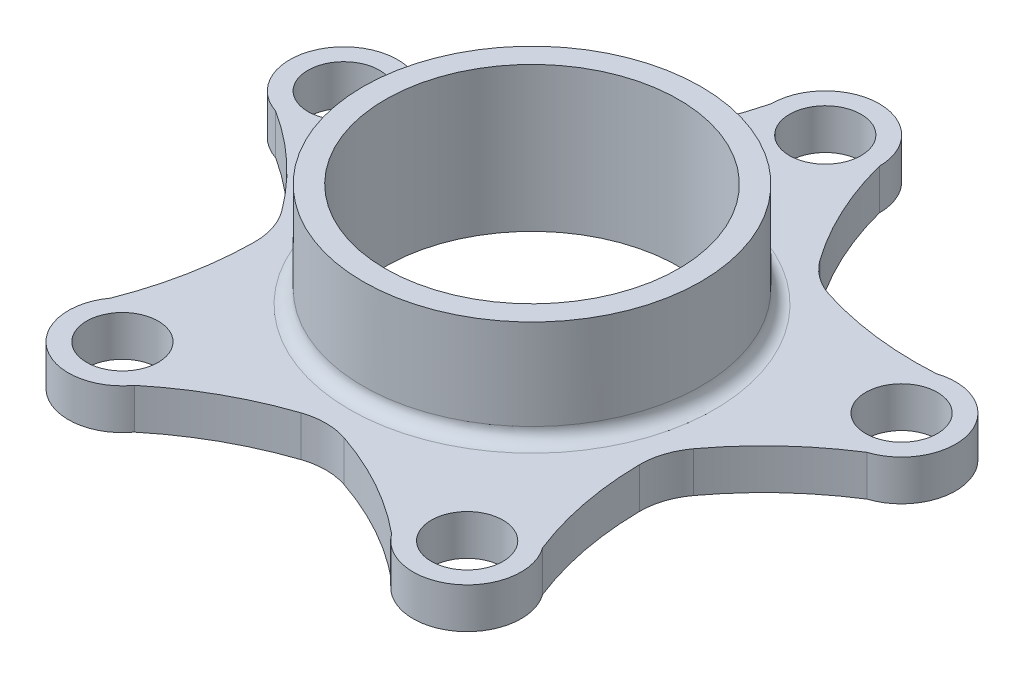
SolidWorks part; units mm, degrees
ref_plane "Front Plane" through (0, 0, 0) normal (0, 0, 1) x (1, 0, 0)
ref_plane "Top Plane" through (0, 0, 0) normal (0, 1, 0) x (1, 0, 0)
ref_plane "Right Plane" through (0, 0, 0) normal (1, 0, 0) x (0, 0, -1)
sketch "Sketch1" plane through (0, 0, 0) normal (0, 1, 0) x (1, 0, 0)
  circle A0 centre (0, 0) radius 31.75
  dimension "D1" = 63.5
extrude "CenterCircleExtrude" add sketch "Sketch1" along normal blind 19.558 contours A0
sketch "Sketch2" plane through (0, 0, 0) normal (0, -1, 0) x (1, 0, 0)
  circle A0 centre (0, 0) radius 80.01
  dimension "D1" = 160.02
extrude "BaseExpand" add sketch "Sketch2" along normal blind 7.62
sketch "Sketch3" plane through (0, 19.558, 0) normal (0, 1, 0) x (1, 0, 0)
  circle A0 centre (0, 0) radius 27.559
  dimension "D1" = 55.118
extrude "CenterCut" cut sketch "Sketch3" against normal blind 27.178 contours A0
sketch "Sketch4" plane through (0, 0, 0) normal (0, 1, 0) x (1, 0, 0)
  line L0 (-52.4203, 17.0324) -> (0, 55.118) construction
  line L1 (-26.2102, 36.0752) -> (-18.6622, 25.6863) construction
  circle A0 centre (0, 55.118) radius 6.731
  circle A1 centre (52.4203, 17.0324) radius 6.731
  circle A2 centre (32.3975, -44.5914) radius 6.731
  circle A3 centre (-32.3975, -44.5914) radius 6.731
  circle A4 centre (-52.4203, 17.0324) radius 6.731
  circle A5 centre (0, 0) radius 31.75 construction
  point P14 (0, 0)
  dimension "D1" = 13.462
  dimension "D2" = 55.118
  dimension "D3" = 5
extrude "OuterCircleCut" cut sketch "Sketch4" against normal blind 7.62
sketch "Sketch8" plane through (0, 0, 0) normal (0, 1, 0) x (1, 0, 0)
  line L0 (-52.4203, 17.0324) -> (0, 55.118) construction
  line L1 (-26.2102, 36.0752) -> (-18.6622, 25.6863) construction
  line L2 (26.2102, 36.0752) -> (18.6622, 25.6863) construction
  line L3 (42.4089, -13.7795) -> (30.196, -9.8113) construction
  line L4 (0, -44.5914) -> (0, -31.75) construction
  line L5 (-42.4089, -13.7795) -> (-30.196, -9.8113) construction
  line L6 (0, 0) -> (-22.4362, 30.8807) construction
  line L7 (0, 0) -> (22.4362, 30.8807) construction
  line L8 (0, 0) -> (10.16, 55.118) construction
  line L9 (10.16, 55.118) -> (-10.16, 55.118) construction
  circle A0 centre (-52.4203, 17.0324) radius 10.16
  circle A1 centre (0, 55.118) radius 10.16
  circle A2 centre (52.4203, 17.0324) radius 10.16
  circle A3 centre (32.3975, -44.5914) radius 10.16
  circle A4 centre (-32.3975, -44.5914) radius 10.16
  circle A5 centre (0, 0) radius 31.75 construction
  arc A6 (10.16, 55.118) -> (22.4362, 30.8807) centre (71.6347, 71.0274) ccw
  arc A7 (-22.4362, 30.8807) -> (-10.16, 55.118) centre (-71.6347, 71.0274) ccw
  arc A8 (22.4362, 30.8807) -> (49.2807, 26.6951) centre (45.4147, 90.0773) ccw
  arc A9 (55.5599, 7.3697) -> (36.3025, -11.7954) centre (89.6874, -46.18) ccw
  arc A10 (36.3025, -11.7954) -> (40.6172, -38.6195) centre (99.7026, -15.3565) ccw
  arc A11 (24.1779, -50.5633) -> (0, -38.1707) centre (-16.2049, -99.5682) ccw
  arc A12 (0, -38.1707) -> (-24.1779, -50.5633) centre (16.2049, -99.5682) ccw
  arc A13 (-40.6172, -38.6195) -> (-36.3025, -11.7954) centre (-99.7026, -15.3565) ccw
  arc A14 (-36.3025, -11.7954) -> (-55.5599, 7.3697) centre (-89.6874, -46.18) ccw
  arc A15 (-49.2807, 26.6951) -> (-22.4362, 30.8807) centre (-45.4147, 90.0773) ccw
  point P14 (0, 0)
  point P27 (0, 0)
  point P72 (0, 0)
  circle M12 centre (0, 0) radius 80.01
  dimension "D1" = 5
  dimension "D3" = 5
  dimension "D5" = 5
  dimension "D4" = 72
  dimension "D2" = 5
extrude "StarfishCut" cut sketch "Sketch8" against normal blind 7.62 contours A0 A15 A7 A1 A6 A8 A2 A9 A10 A3 A11 A12 A4 A13 A14 M12 region at (-77.747, 0, 0)
fillet "Fillet8" radius 2.54 1 edges at (0, 0, 31.75)
fillet "Fillet10" radius 12.7 5 edges at (-22.4362, -3.81, -30.8807) (-36.3025, -3.81, 11.7954) (0, -3.81, 38.1707) (36.3025, -3.81, 11.7954) (22.4362, -3.81, -30.8807)
